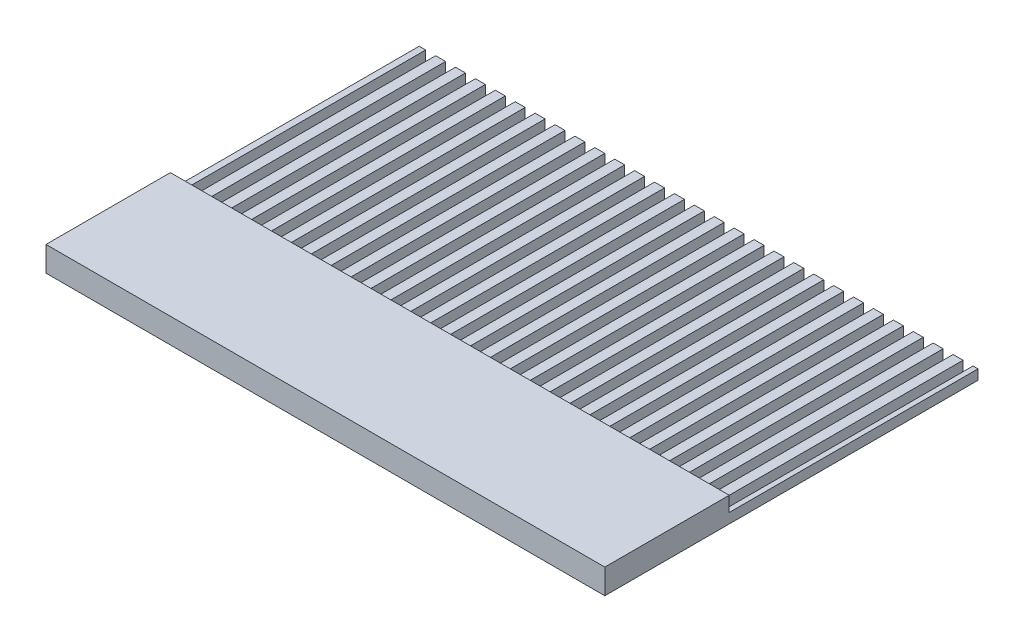
SolidWorks part; units mm, degrees
ref_plane "Front Plane" through (0, 0, 0) normal (0, 0, 1) x (1, 0, 0)
ref_plane "Top Plane" through (0, 0, 0) normal (0, 1, 0) x (1, 0, 0)
ref_plane "Right Plane" through (0, 0, 0) normal (1, 0, 0) x (0, 0, -1)
sketch "Sketch1" plane through (0, 0, 0) normal (0, 1, 0) x (1, 0, 0)
  line L1 (0, 0) -> (115, 0)
  line L2 (0, 0) -> (0, 15)
  line L3 (0, 15) -> (115, 15)
  line L4 (115, 0) -> (115, 15)
extrude "Boss-Extrude1" add sketch "Sketch1" along normal blind 0.5
sketch "Sketch2" plane through (0, 0.5, 0) normal (0, 1, 0) x (1, 0, 0)
  line L0 (115, 0) -> (115, 15) construction
  line L1 (0, 15) -> (115, 15)
  line L2 (0, 15) -> (0, 5)
  line L3 (0, 5) -> (115, 5)
  line L4 (115, 15) -> (115, 5)
extrude "Cut-Extrude1" cut sketch "Sketch2" against normal blind 0.1
sketch "Sketch3" plane through (0, 0.4, 0) normal (0, 1, 0) x (1, 0, 0)
  line L0 (0, 5) -> (115, 5) construction
  line L1 (0, 15) -> (0.4, 15)
  line L2 (0, 15) -> (0, 5)
  line L3 (0, 5) -> (0.4, 5)
  line L4 (0.4, 15) -> (0.4, 5)
extrude "Cut-Extrude2" cut sketch "Sketch3" against normal blind 0.4
pattern_linear "LPattern3" count 150 spacing 0.8 along (1, 0, 0) of "Cut-Extrude2"
sketch "Sketch4" plane through (0, 0, 0) normal (0, -1, 0) x (1, 0, 0)
  line L0 (0, -5) -> (0, 0) construction
  line L1 (0, -5) -> (115, -5)
  line L2 (0, -5) -> (0, 0)
  line L3 (0, 0) -> (115, 0)
  line L4 (115, -5) -> (115, 0)
  line L5 (0, -5) -> (0.4, -5) construction
extrude "Boss-Extrude2" add sketch "Sketch4" against normal blind 1
sketch "Sketch5" plane through (0, 1, 0) normal (0, 1, 0) x (1, 0, 0)
  line L1 (0, 0) -> (77.2891, 0)
  line L2 (0, 0) -> (0, 15.8221)
  line L3 (0, 15.8221) -> (77.2891, 15.8221)
  line L4 (77.2891, 0) -> (77.2891, 15.8221)
extrude "Cut-Extrude3" cut sketch "Sketch5" against normal blind 1
sketch "Sketch6" plane through (0, 1, 0) normal (0, 1, 0) x (1, 0, 0)
  line L1 (77.2891, 0) -> (80.4862, 0)
  line L2 (77.2891, 0) -> (77.2891, 15.0666)
  line L3 (77.2891, 15.0666) -> (80.4862, 15.0666)
  line L4 (80.4862, 0) -> (80.4862, 15.0666)
extrude "Cut-Extrude4" cut sketch "Sketch6" against normal blind 1
sketch "Sketch7" plane through (0, 1, 0) normal (0, 1, 0) x (1, 0, 0)
  line L0 (115, 0) -> (80.4862, 0) construction
  line L1 (80.4862, 0) -> (92.5384, 0)
  line L2 (80.4862, 0) -> (80.4862, 15.1262)
  line L3 (80.4862, 15.1262) -> (92.5384, 15.1262)
  line L4 (92.5384, 0) -> (92.5384, 15.1262)
  point P5 (91.1601, 0)
  point P8 (92.5384, 0)
extrude "Cut-Extrude5" cut sketch "Sketch7" against normal blind 10
